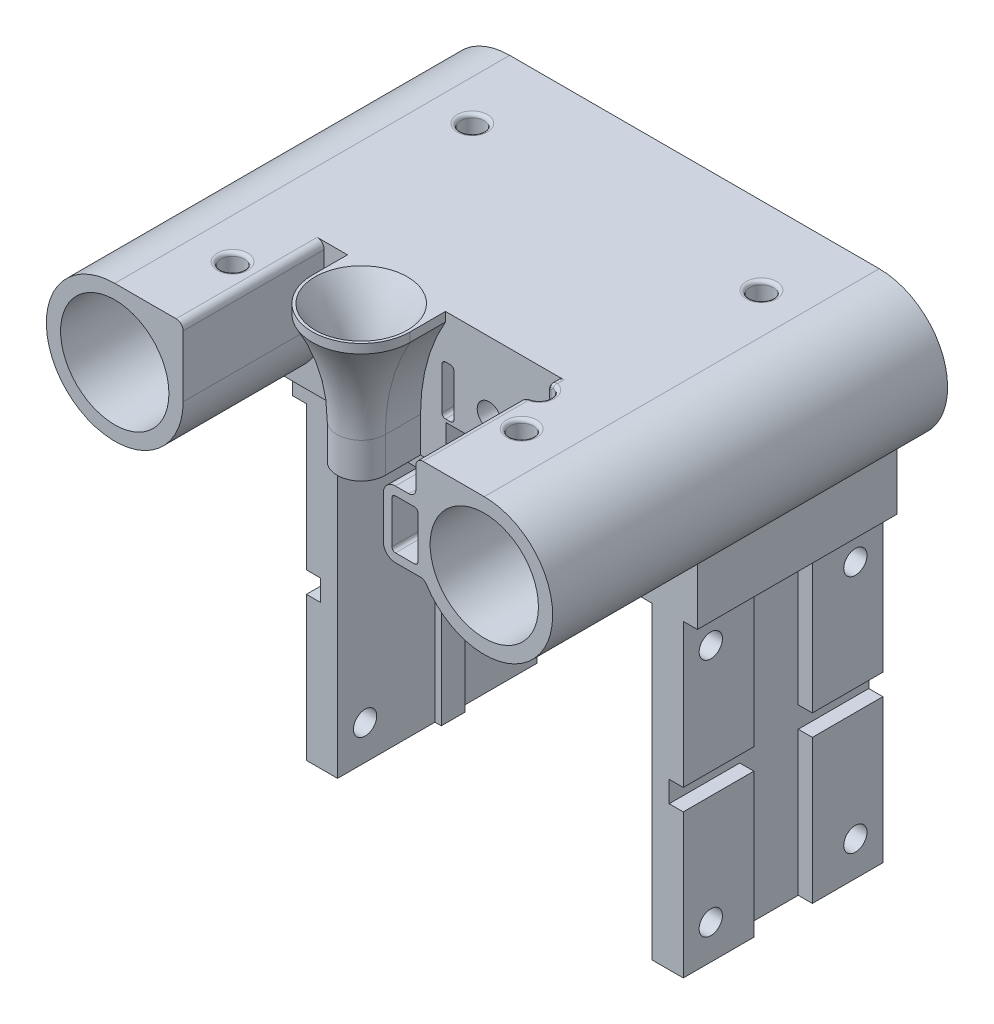
SolidWorks part; units mm, degrees
ref_plane "Front Plane" through (0, 0, 0) normal (0, 0, 1) x (1, 0, 0)
ref_plane "Top Plane" through (0, 0, 0) normal (0, 1, 0) x (1, 0, 0)
ref_plane "Right Plane" through (0, 0, 0) normal (1, 0, 0) x (0, 0, -1)
sketch "Sketch1" plane through (0, 0, 0) normal (0, 0, 1) x (1, 0, 0)
  line L87 (-26.2, 9.7) -> (26.2, 9.7)
  line L93 (-22.3, -19.2) -> (-22.3, -63)
  line L112 (22.3, -19.2) -> (22.3, -63)
  line L113 (-22.3, -19.2) -> (22.3, -19.2)
  line L122 (-26.72, -63) -> (-22.3, -63)
  line L123 (22.3, -63) -> (26.72, -63)
  line L127 (-26.72, -63) -> (-26.72, -42.6)
  line L129 (26.72, -63) -> (26.72, -42.6)
  line L139 (0.7, 3.5) -> (1.4016, 3.5)
  line L140 (0.2, 3) -> (0.2, -3)
  line L141 (0.7, -3.5) -> (1.4016, -3.5)
  line L142 (1.9016, 3) -> (1.9016, -3)
  line L143 (13.6, 3.5) -> (16.3, 3.5)
  line L144 (13.1, 3) -> (13.1, -3)
  line L145 (13.6, -3.5) -> (16.3, -3.5)
  line L146 (16.8, 3) -> (16.8, -3)
  line L151 (-28.72, -19.2) -> (-28.72, -9.3669)
  line L152 (26.72, -19.2) -> (28.72, -19.2)
  line L153 (28.72, -19.2) -> (28.72, -9.3669)
  line L154 (-28.72, -19.2) -> (-26.72, -19.2)
  line L155 (-26.72, -39.6) -> (-24.72, -39.6)
  line L157 (-26.72, -42.6) -> (-24.72, -42.6)
  line L158 (-24.72, -39.6) -> (-24.72, -42.6)
  line L159 (24.72, -39.6) -> (26.72, -39.6)
  line L160 (24.72, -39.6) -> (24.72, -42.6)
  line L161 (24.72, -42.6) -> (26.72, -42.6)
  line L163 (-26.72, -39.6) -> (-26.72, -19.2)
  line L164 (26.72, -39.6) -> (26.72, -19.2)
  circle A67 centre (26.2, 0) radius 7.68
  circle A68 centre (-26.2, 0) radius 7.68
  arc A87 (-26.2, 9.7) -> (-28.72, -9.3669) centre (-26.2, 0) ccw
  arc A88 (28.72, -9.3669) -> (26.2, 9.7) centre (26.2, 0) ccw
  arc A89 (16.3, 3.5) -> (16.8, 3) centre (16.3, 3) cw
  arc A90 (16.3, -3.5) -> (16.8, -3) centre (16.3, -3) ccw
  arc A91 (13.1, -3) -> (13.6, -3.5) centre (13.6, -3) ccw
  arc A92 (13.6, 3.5) -> (13.1, 3) centre (13.6, 3) ccw
  arc A93 (1.9016, 3) -> (1.4016, 3.5) centre (1.4016, 3) ccw
  arc A94 (1.4016, -3.5) -> (1.9016, -3) centre (1.4016, -3) ccw
  arc A95 (0.2, -3) -> (0.7, -3.5) centre (0.7, -3) ccw
  arc A96 (0.7, 3.5) -> (0.2, 3) centre (0.7, 3) ccw
  circle A101 centre (6.9, 0) radius 1.7
extrude "Boss-Extrude1" add sketch "Sketch1" along normal blind 56
sketch "Sketch3" plane through (0, 0, 56) normal (0, 0, 1) x (1, 0, 0)
  line L0 (-26.72, -19.2) -> (-28.72, -19.2)
  line L9 (-28.72, -19.2) -> (-28.72, -9.3669)
  line L10 (-26.72, -63) -> (26.72, -63)
  line L11 (-26.72, -63) -> (-26.72, -19.2)
  line L12 (-26.2, -9.7) -> (26.2, -9.7)
  line L13 (26.72, -63) -> (26.72, -19.2)
  line L14 (26.72, -19.2) -> (28.72, -19.2)
  line L15 (28.72, -19.2) -> (28.72, -9.3669)
  arc A0 (-28.72, -9.3669) -> (-26.2, -9.7) centre (-26.2, 0) ccw
  arc A1 (26.2, -9.7) -> (28.72, -9.3669) centre (26.2, 0) ccw
extrude "Cut-Extrude1" cut sketch "Sketch3" against normal offset from surface (27.7 mm away) 28.3 up to face at (-18.52, 0, 0)
sketch "Sketch6" plane through (0, -19.2, 0) normal (0, -1, 0) x (1, 0, 0)
  line L1 (-9, 0) -> (9, 0)
  line L2 (-9, 0) -> (-9, 10)
  line L3 (-9, 10) -> (9, 10)
  line L4 (9, 0) -> (9, 10)
extrude "Cut-Extrude4" cut sketch "Sketch6" against normal blind 9.5
sketch "Sketch8" plane through (-26.72, 0, 0) normal (-1, 0, 0) x (0, 0, 1)
  circle A0 centre (3.9, -24.1) radius 1.65
  circle A1 centre (3.9, -58.1) radius 1.65
  circle A2 centre (24.4, -58.1) radius 1.65
  circle A3 centre (24.4, -24.1) radius 1.65
extrude "Cut-Extrude6" cut sketch "Sketch8" against normal up to surface (53.44 mm away) up to face at (26.72, -52.8, 14.15)
sketch "Sketch9" plane through (0, 0, 0) normal (0, 0, 1) x (1, 0, 0)
  line L1 (-22.3, -63) -> (-21.4, -63)
  line L2 (-22.3, -63) -> (-22.3, -19.2)
  line L3 (-22.3, -19.2) -> (22.3, -19.2)
  line L4 (22.3, -63) -> (22.3, -19.2)
  line L6 (21.4, -63) -> (22.3, -63)
  line L7 (15.0218, -19.7) -> (-15.0218, -19.7)
  line L18 (-21.4, -26.0782) -> (-21.4, -63)
  line L19 (15.0218, -19.7) -> (21.4, -26.0782)
  line L20 (21.4, -63) -> (21.4, -26.0782)
  line L22 (-21.4, -26.0782) -> (-15.0218, -19.7)
extrude "Boss-Extrude2" add sketch "Sketch9" along normal blind 3.4 from offset 11.1
sketch "Sketch11" plane through (0, 0, 0) normal (0, 0, 1) x (1, 0, 0)
  line L1 (-26.72, -19.2) -> (-24.72, -19.2)
  line L2 (-26.72, -19.2) -> (-26.72, -63)
  line L3 (-26.72, -63) -> (-24.72, -63)
  line L4 (-24.72, -19.2) -> (-24.72, -63)
  line L6 (26.72, -19.2) -> (24.72, -19.2)
  line L7 (26.72, -19.2) -> (26.72, -63)
  line L8 (26.72, -63) -> (24.72, -63)
  line L9 (24.72, -19.2) -> (24.72, -63)
extrude "Cut-Extrude8" cut sketch "Sketch11" along normal offset from surface (8.3 mm away) 10 from offset 10 up to face at (0, -33.3773, 28.3)
sketch "Sketch12" plane through (0, 9.7, 0) normal (0, 1, 0) x (1, 0, 0)
  circle A0 centre (17, -39) radius 1.65
extrude "Cut-Extrude9" cut sketch "Sketch12" against normal up to surface (19.4 mm away) up to face at (0, -9.7, 42.15)
sketch "Sketch13" plane through (0, 0, 56) normal (0, 0, 1) x (1, 0, 0)
  line L1 (-17.5, 9.7) -> (17.5, 9.7)
  line L6 (-16.5, 0) -> (-16.5, 8.7)
  line L8 (26.2, -9.7) -> (-26.2, -9.7)
  line L9 (16.5, 8.7) -> (16.5, 5.71)
  line L20 (13.6, 4.71) -> (15.5, 4.71)
  line L21 (11.89, 3) -> (11.89, -3)
  line L22 (13.6, -4.71) -> (17.1509, -4.71)
  arc A0 (-26.2, -9.7) -> (-16.5, 0) centre (-26.2, 0) ccw
  arc A9 (-16.5, 8.7) -> (-17.5, 9.7) centre (-17.5, 8.7) ccw
  arc A10 (17.5, 9.7) -> (16.5, 8.7) centre (17.5, 8.7) ccw
  arc A11 (17.9966, -5.1763) -> (26.2, -9.7) centre (26.2, 0) ccw
  arc A13 (13.6, 4.71) -> (11.89, 3) centre (13.6, 3) ccw
  arc A14 (11.89, -3) -> (13.6, -4.71) centre (13.6, -3) ccw
  arc A15 (17.1509, -4.71) -> (17.9966, -5.1763) centre (17.1509, -5.71) cw
  arc A16 (16.5, 5.71) -> (15.5, 4.71) centre (15.5, 5.71) cw
extrude "Cut-Extrude10" cut sketch "Sketch13" against normal blind 20
sketch "Sketch7" plane through (0, -19.2, 0) normal (0, -1, 0) x (1, 0, 0)
  line L1 (0.8, 25) -> (10.8, 25)
  line L2 (0.8, 25) -> (0.8, 53)
  line L3 (0.8, 53) -> (10.8, 53)
  line L4 (10.8, 25) -> (10.8, 53)
extrude "Cut-Extrude11" cut sketch "Sketch7" against normal blind 15.29
sketch "Sketch14" plane through (0, 9.7, 0) normal (0, 1, 0) x (1, 0, 0)
  line L7 (0.7, -41) -> (0.7, -36)
  line L10 (0.7, -36) -> (-13.2, -36)
  line L12 (-13.2, -36) -> (-13.2, -41)
  arc A4 (-13.2, -41) -> (0.7, -41) centre (-6.25, -41) ccw
extrude "Boss-Extrude4" add sketch "Sketch14" against normal up to surface (19.4 mm away) up to face at (-12.7, -9.7, 32.15)
sketch "Sketch15" plane through (0, 9.7, 0) normal (0, 1, 0) x (1, 0, 0)
  circle A0 centre (20.5, -45) radius 1.65
  circle A1 centre (20.5, -11) radius 1.65
  circle A2 centre (-20.5, -11) radius 1.65
  circle A3 centre (-20.5, -45) radius 1.65
extrude "Cut-Extrude12" cut sketch "Sketch15" against normal up to next
fillet "Fillet1" radius 0.5 29 edges at (16.7095, 9.3124, 40.6242) (16.9444, 9.5315, 37.3509) (16.6128, 3.3901, 37.3961) (15.35, 3.5, 39) (16.6929, 3.3092, 40.6212) (16.8, 0, 40.6378) (16.6128, -3.3901, 40.6039) (15.35, -3.5, 39) (16.6929, -3.3092, 37.3788) (18.6457, -6.0846, 38.8806) (-20.2148, 4.8125, 9.3748) (-20.5, 9.7, 12.65) (-20.5, 9.7, 46.65) (20.5, 9.7, 46.65) (20.5, 9.7, 12.65) (19.5441, 3.8316, 43.6551) (19.5441, 3.8316, 9.6551) (18.5461, 0.6323, 38.4237) (18.65, 9.7, 39) (16.8, 0, 37.3622) (-20.2148, 4.8125, 43.3748) (16.5, 7.205, 40.5724) (16.2628, 5.0634, 40.4762) (15.35, 4.71, 39) (16.1054, 4.9141, 37.6136) (16.5, 7.205, 37.4276) (17.7544, -4.9126, 40.4675) (17.7232, -4.8899, 37.5169) (15.35, -4.71, 39)
sketch "Sketch17" plane through (0, 0, 0) normal (0, 0, -1) x (-1, 0, 0)
  line L1 (-9.9, -6.5) -> (1.1, -6.5)
  line L2 (3.1, -4.5) -> (3.1, 4.5)
  line L3 (1.1, 6.5) -> (-9.9, 6.5)
  line L4 (-11.9, 4.5) -> (-11.9, -4.5)
  arc A0 (-11.9, 4.5) -> (-9.9, 6.5) centre (-9.9, 4.5) cw
  arc A1 (1.1, 6.5) -> (3.1, 4.5) centre (1.1, 4.5) cw
  arc A2 (3.1, -4.5) -> (1.1, -6.5) centre (1.1, -4.5) cw
  arc A3 (-9.9, -6.5) -> (-11.9, -4.5) centre (-9.9, -4.5) cw
extrude "Cut-Extrude13" cut sketch "Sketch17" against normal offset from surface (20 mm away) 16 up to face at (9.1265, -0.8232, 36)
sketch "Sketch18" plane through (0, 0, 20) normal (0, 0, -1) x (-1, 0, 0)
  line L1 (-0.7, 3.5) -> (-2.3, 3.5)
  line L2 (-0.2, 3) -> (-0.2, -3)
  line L3 (-0.7, -3.5) -> (-2.3, -3.5)
  line L4 (-2.8, 3) -> (-2.8, -3)
  arc A0 (-0.7, 3.5) -> (-0.2, 3) centre (-0.7, 3) cw
  arc A1 (-0.2, -3) -> (-0.7, -3.5) centre (-0.7, -3) cw
  arc A2 (-2.3, -3.5) -> (-2.8, -3) centre (-2.3, -3) cw
  arc A3 (-2.3, 3.5) -> (-2.8, 3) centre (-2.3, 3) ccw
extrude "Cut-Extrude14" cut sketch "Sketch18" against normal offset from surface (8 mm away) 8 up to face at (9.1265, -0.8232, 36)
ref_plane "Plane1" through (0, 0, 41) normal (0, 0, -1) x (-1, 0, 0)
sketch "Sketch19" plane through (0, 0, 41) normal (0, 0, -1) x (-1, 0, 0)
  line L0 (6.25, 9.7) -> (6.25, -9.7) construction
  line L3 (6.25, -9.7) -> (4.05, -9.7)
  line L6 (4.05, -9.7) -> (4.05, -4.7)
  line L14 (6.25, 9.7) -> (6.25, -9.7)
  line L15 (6.25, 9.7) -> (-0.3, 9.7)
  arc A1 (4.05, -4.7) -> (-0.3, 9.7) centre (-21.9595, -4.7) ccw
revolve "Cut-Revolve1" cut sketch "Sketch19" angle 360 about L0
sketch "Sketch23" plane through (0, 0, 41) normal (0, 0, -1) x (-1, 0, 0)
  line L0 (6.25, -9.7) -> (6.25, 9.7) construction
  line L14 (2.84, -9.7) -> (2.84, -4.7)
  line L21 (2.84, -9.7) -> (-0.7, -9.7)
  line L22 (-0.7, -9.7) -> (-0.7, 8.4002)
  arc A3 (2.84, -4.7) -> (-0.7, 8.4002) centre (-23.1695, -4.7) ccw
revolve "Cut-Revolve2" cut sketch "Sketch23" angle 180 about L0 reverse direction yes
sketch "Sketch24" plane through (0, 0, 41) normal (0, 0, 1) x (1, 0, 0)
  line L0 (-9.66, -9.7) -> (-9.66, -4.7)
  line L1 (-9.66, -9.7) -> (-13.2, -9.7)
  line L2 (-13.2, -9.7) -> (-13.2, 8.4002)
  line L5 (0.7, -9.7) -> (0.7, 8.4002)
  line L6 (-2.84, -9.7) -> (0.7, -9.7)
  line L7 (-2.84, -9.7) -> (-2.84, -4.7)
  arc A0 (-9.66, -4.7) -> (-13.2, 8.4002) centre (-35.6695, -4.7) ccw
  arc A2 (-2.84, -4.7) -> (0.7, 8.4002) centre (23.1695, -4.7) cw
extrude "Cut-Extrude15" cut sketch "Sketch24" against normal up to surface (5 mm away) up to face at (-16.814, 1.1497, 36)
